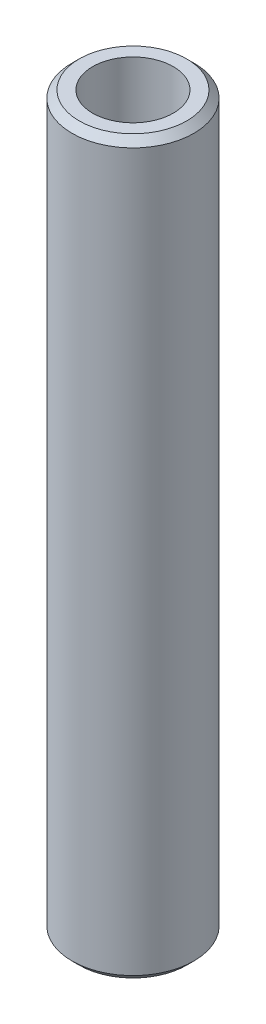
SolidWorks part; units mm, degrees
ref_plane "Front Plane" through (0, 0, 0) normal (0, 0, 1) x (1, 0, 0)
ref_plane "Top Plane" through (0, 0, 0) normal (0, 1, 0) x (1, 0, 0)
ref_plane "Right Plane" through (0, 0, 0) normal (1, 0, 0) x (0, 0, -1)
sketch "Sketch1" plane through (0, 0, 0) normal (0, 1, 0) x (1, 0, 0)
  circle A0 centre (0, 0) radius 50
  dimension "SHAFT_OD" = 100
extrude "Boss-Extrude1" add sketch "Sketch1" along normal blind 600
sketch "Sketch2" plane through (0, 0, 0) normal (0, 1, 0) x (1, 0, 0)
  circle A0 centre (0, 0) radius 33.1161
  dimension "BORE_D" = 66.2323
extrude "Cut-Extrude1" cut sketch "Sketch2" along normal through all
chamfer "Chamfer1" distance 5.8804 angle 45 2 edges at (0, 600, 50) (0, 0, 50)
